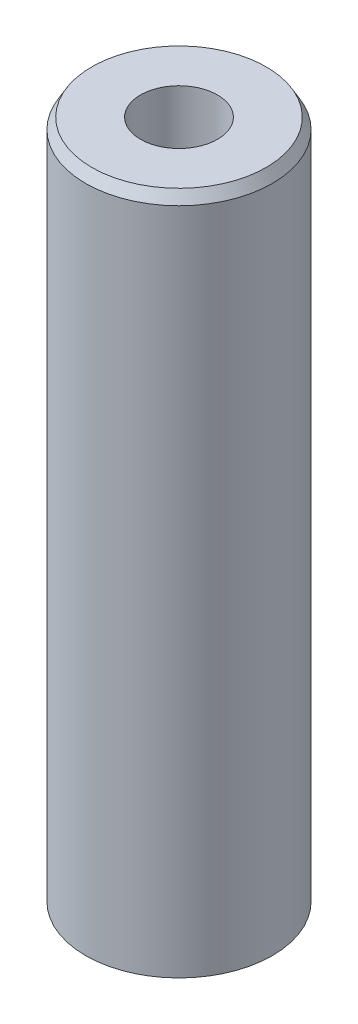
SolidWorks part; units mm, degrees
ref_plane "Front Plane" through (0, 0, 0) normal (0, 0, 1) x (1, 0, 0)
ref_plane "Top Plane" through (0, 0, 0) normal (0, 1, 0) x (1, 0, 0)
ref_plane "Right Plane" through (0, 0, 0) normal (1, 0, 0) x (0, 0, -1)
sketch "Sketch1" plane through (0, 0, 0) normal (0, 1, 0) x (1, 0, 0)
  circle A0 centre (0, 0) radius 47.5
  dimension "SHAFT_OD" = 95
extrude "Boss-Extrude1" add sketch "Sketch1" along normal blind 348.7557
sketch "Sketch2" plane through (0, 0, 0) normal (0, 1, 0) x (1, 0, 0)
  circle A0 centre (0, 0) radius 19.5746
  dimension "BORE_D" = 39.1491
extrude "Cut-Extrude1" cut sketch "Sketch2" along normal through all
chamfer "Chamfer1" distance 5.4608 angle 30 2 edges at (0, 348.7557, 47.5) (0, 0, 47.5) first distance on face at (0, 348.7557, 47.5) first distance on face at (0, 0, 19.5746)
